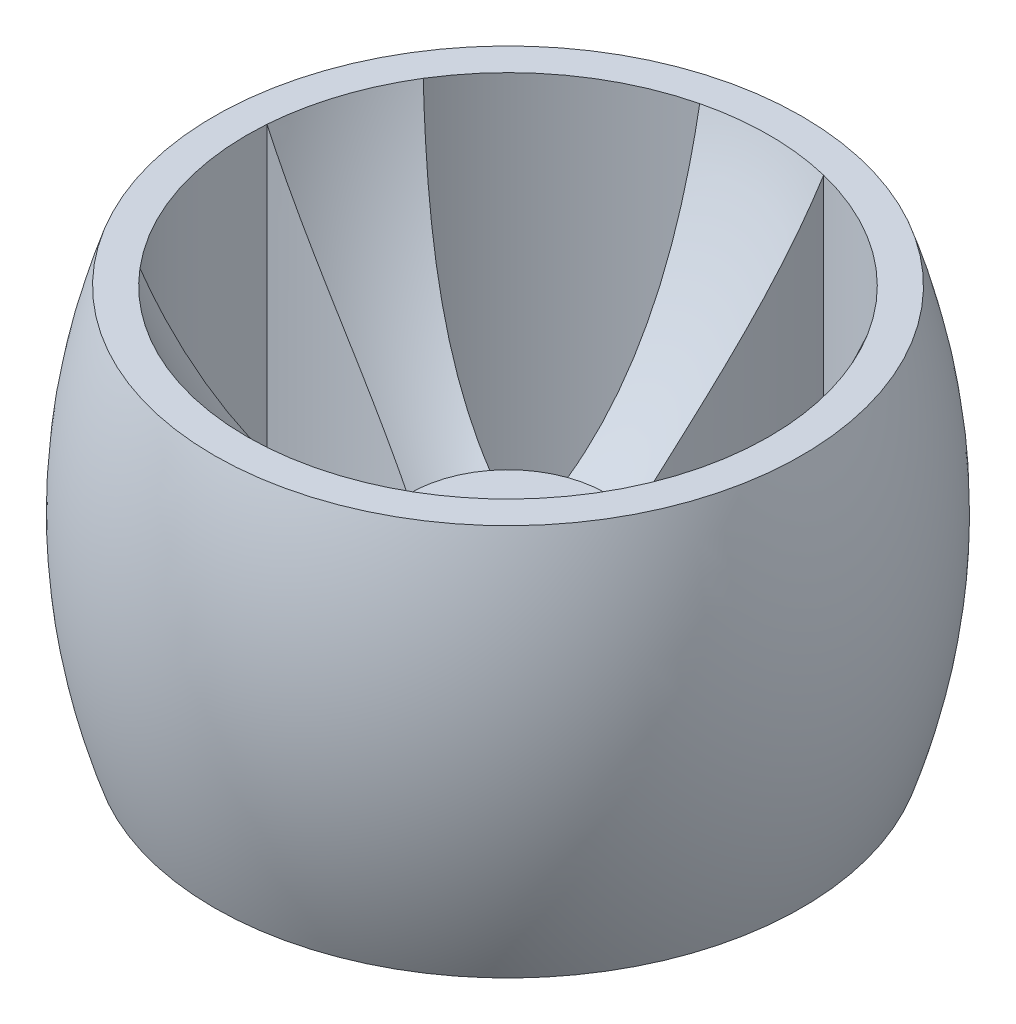
SolidWorks part; units mm, degrees
ref_plane "Front Plane" through (0, 0, 0) normal (0, 0, 1) x (1, 0, 0)
ref_plane "Top Plane" through (0, 0, 0) normal (0, 1, 0) x (1, 0, 0)
ref_plane "Right Plane" through (0, 0, 0) normal (1, 0, 0) x (0, 0, -1)
sketch "Sketch1" plane through (0, 0, 0) normal (0, 1, 0) x (1, 0, 0)
  line L0 (0, 6) -> (0, 8) construction
  line L1 (-2, 8) -> (2, 8)
  line L2 (-2, 8) -> (-2, 5.6569)
  line L3 (2, 8) -> (2, 5.6569)
  line L4 (0, 0) -> (0, 40) construction
  line L5 (-10, 40) -> (10, 40) construction
  line L6 (-5, 20) -> (5, 20) construction
  line L7 (-10, 0) -> (10, 0)
  circle A0 centre (0, 0) radius 6
  circle A1 centre (0, 0) radius 45
  circle A2 centre (0, 0) radius 40
  circle A3 centre (0, 0) radius 15
  circle A4 centre (-10, 0) radius 2.5
  circle A5 centre (10, 0) radius 2.5
  spline S0 degree 2 poles (-10, 40) (-4.2896, 27.4663) (-5, 14.1421) knots 0 0 0 1 1 1
  spline S1 degree 2 poles (10, 40) (4.2896, 27.4663) (5, 14.1421) knots 0 0 0 1 1 1
  spline S2 degree 2 poles (34.9521, 21.8712) (24.7964, 12.5672) (11.9049, 9.1254) knots 0 0 0 1 1 1
  spline S3 degree 2 poles (41.1324, 2.8501) (27.4476, 4.4079) (14.9951, -0.3851) knots 0 0 0 1 1 1
  spline S4 degree 2 poles (31.6016, -26.4828) (19.6147, -19.6993) (12.3576, -8.5023) knots 0 0 0 1 1 1
  spline S5 degree 2 poles (15.4212, -38.2385) (12.6739, -24.7421) (4.2675, -14.3802) knots 0 0 0 1 1 1
  spline S6 degree 2 poles (-15.4212, -38.2385) (-12.6739, -24.7421) (-4.2675, -14.3802) knots 0 0 0 1 1 1
  spline S7 degree 2 poles (-31.6016, -26.4828) (-19.6147, -19.6993) (-12.3576, -8.5023) knots 0 0 0 1 1 1
  spline S8 degree 2 poles (-41.1324, 2.8501) (-27.4476, 4.4079) (-14.9951, -0.3851) knots 0 0 0 1 1 1
  spline S9 degree 2 poles (-34.9521, 21.8712) (-24.7964, 12.5672) (-11.9049, 9.1254) knots 0 0 0 1 1 1
  point P8 (0, 8)
  point P17 (0, 40)
  point P20 (0, 20)
  point P50 (0, 0)
  point P52 (0, 0)
  dimension "D1" = 12
  dimension "D4" = 90
  dimension "D5" = 30
  dimension "D6" = 80
  dimension "D10" = 5
  dimension "D11" = 5
  dimension "D2" = 2
  dimension "D3" = 4
  dimension "D7" = 20
  dimension "D8" = 10
  dimension "D9" = 20
extrude "Boss-Extrude1" add sketch "Sketch1" along normal blind 15 contours A3 A0 L2 L1 L3 region at (13.8623, 0, 4.5042)
extrude "Boss-Extrude2" add sketch "Sketch1<3>" along normal blind 50 and the other way blind 10 contours A1 A2 | S3 A2 S2 A3 | S1 A2 S0 A3 | S9 A2 S8 A3 | S7 A2 S6 A3 | S5 A2 S4 A3 region at (-43.7272, 0, 0) region at (27.3249, 0, -8.8784) region at (16.8877, 0, 23.244) region at (0, 0, -28.7312) region at (-16.8877, 0, 23.244) region at (-27.3249, 0, -8.8784)
sketch "Sketch1<3>" plane through (0, 0, 0) normal (0, 1, 0) x (1, 0, 0) same geometry as "Sketch1"
sketch "Sketch2" plane through (0, 0, 0) normal (0, 0, 1) x (1, 0, 0)
  line L0 (45, 50) -> (45, -10)
  line L1 (45, 20) -> (50, 20)
  spline S0 degree 2 poles (45, 50) (55, 20) (45, -10) knots 0 0 0 1 1 1
  dimension "D1" = 5
revolve "Revolve1" add sketch "Sketch2" angle 360 about axis through (0, -10, 0) along (0, 1, 0) region at (47, 31.25, 0) region at (47, 8.75, 0)
sketch "Sketch4" plane through (0, 0, 0) normal (0, 0, 1) x (1, 0, 0)
  line L0 (0, -10) -> (0, 50) construction
  line L1 (-45, -10) -> (45, -10) construction
  line L2 (15.1594, 50) -> (-15.1594, 50) construction
  line L3 (-40, 50) -> (40, 50)
  line L4 (45, 50) -> (-45, 50) construction
  line L5 (-40, -10) -> (40, -10)
  line L6 (-15, 15) -> (15, 15)
  line L7 (-15, 0) -> (15, 0)
  line L8 (-25, 25) -> (25, 25)
  line L9 (-25, -2.5) -> (25, -2.5)
  spline S0 degree 2 poles (-40, 50) (-31.6697, 29.2444) (-15, 15) knots 0 0 0 1 1 1
  spline S1 degree 2 poles (-40, -10) (-28.5251, -2.2288) (-15, 0) knots 0 0 0 1 1 1
  spline S2 degree 2 poles (40, -10) (28.5251, -2.2288) (15, 0) knots 0 0 0 1 1 1
  spline S3 degree 2 poles (40, 50) (31.6697, 29.2444) (15, 15) knots 0 0 0 1 1 1
  point P11 (0, 50)
  point P14 (0, -10)
  point P17 (0, 15)
  point P20 (0, 0)
  point P23 (0, 25)
  point P26 (0, -2.5)
  dimension "D1" = 80
  dimension "D2" = 80
  dimension "D3" = 35
  dimension "D4" = 10
  dimension "D5" = 30
  dimension "D6" = 30
  dimension "D7" = 25
  dimension "D8" = 50
  dimension "D9" = 50
  dimension "D10" = 2.5
revolve "Cut-Revolve1" cut sketch "Sketch4" angle 360 about L0 region at (-16.9425, -6.5258, 0) region at (-10.3371, 20.4103, 0) region at (-10.4874, -1.3489, 0) region at (-16.9909, 38.4267, 0)
